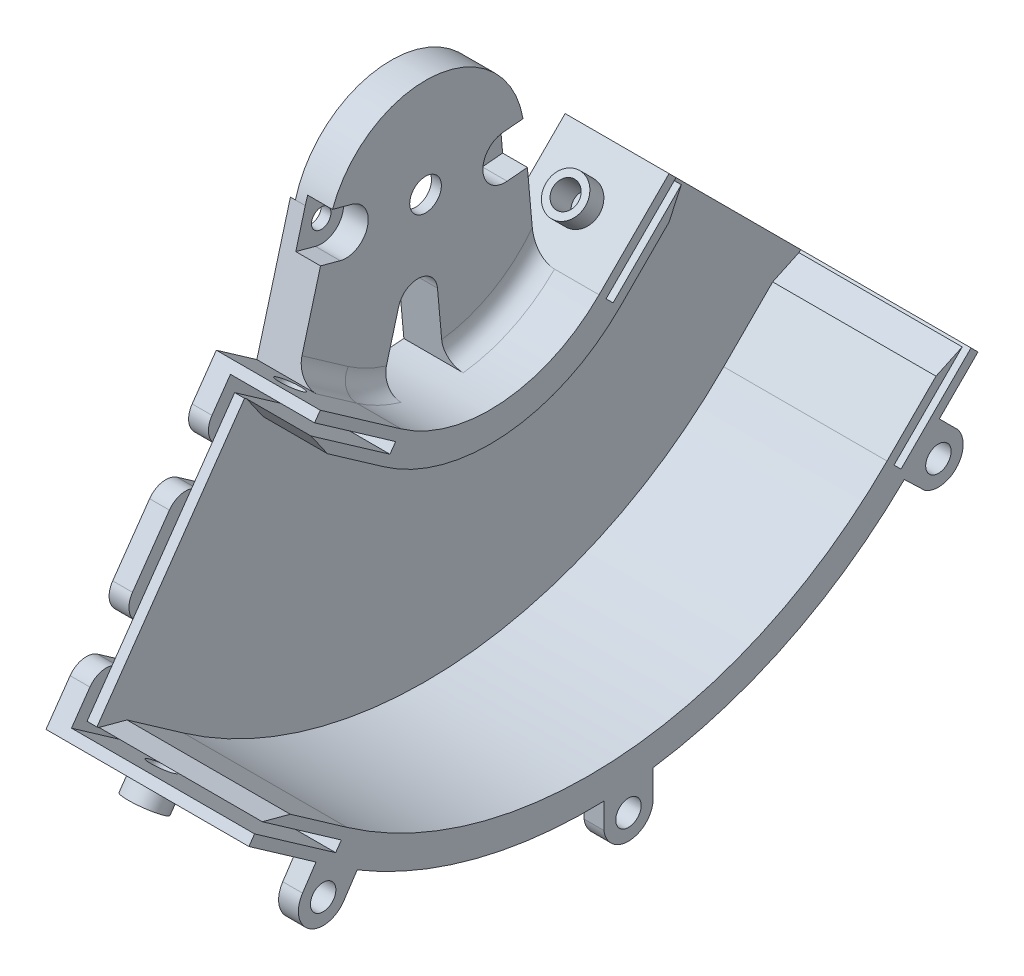
SolidWorks part; units mm, degrees
ref_plane "Front Plane" through (0, 0, 0) normal (0, 0, 1) x (1, 0, 0)
ref_plane "Top Plane" through (0, 0, 0) normal (0, 1, 0) x (1, 0, 0)
ref_plane "Right Plane" through (0, 0, 0) normal (1, 0, 0) x (0, 0, -1)
sketch "Sketch3" plane through (0, 0, 0) normal (1, 0, 0) x (0, 0, -1)
  line L0 (-22.7274, -32.4581) -> (-62.0633, -88.6355)
  line L1 (28.0184, -28.0184) -> (76.5118, -76.5118)
  line L2 (-22.7274, -32.4581) -> (0, 0) construction
  line L3 (0, 0) -> (28.0184, -28.0184) construction
  line L4 (0, 40.513) -> (0, -40.513) construction
  line L5 (-62.0633, -88.6355) -> (-66.4339, -94.8775)
  line L6 (76.5118, -76.5118) -> (81.8999, -81.8999)
  arc A2 (-62.0633, -88.6355) -> (76.5118, -76.5118) centre (0, 0) ccw
  arc A4 (-27.098, -38.7) -> (33.4066, -33.4066) centre (0, 0) ccw
  arc A5 (-22.7274, -32.4581) -> (28.0184, -28.0184) centre (0, 0) ccw
  arc A6 (-66.4339, -94.8775) -> (81.8999, -81.8999) centre (0, 0) ccw
  dimension "D1" = 216.408
  dimension "D2" = 135
  dimension "D3" = 94.488
  dimension "D4" = 7.62
  dimension "D6" = 7.62
  dimension "D5" = 80
extrude "Base extrude" add sketch "Sketch3" along normal blind 58.42 contours L5 A6 L6 A2 | A5 L0 A4 L1 region at (0, -39.9408, -3.4944) region at (0, -109.321, -9.5643)
sketch "Sketch4" plane through (58.42, 0, 0) normal (1, 0, 0) x (0, 0, -1)
  line L0 (-66.4339, -94.8775) -> (-22.7274, -32.4581)
  line L1 (28.0184, -28.0184) -> (81.8999, -81.8999)
  arc A0 (-22.7274, -32.4581) -> (28.0184, -28.0184) centre (0, 0) ccw
  arc A1 (-22.7274, -32.4581) -> (28.0184, -28.0184) centre (0, 0) ccw construction
  arc A2 (-66.4339, -94.8775) -> (81.8999, -81.8999) centre (0, 0) ccw
  arc A3 (-66.4339, -94.8775) -> (81.8999, -81.8999) centre (0, 0) ccw construction
  arc M1 (28.0184, -28.0184) -> (-22.7274, -32.4581) centre (0, 0) cw
  line M2 (-22.7274, -32.4581) -> (-27.098, -38.7)
  arc M3 (-27.098, -38.7) -> (33.4066, -33.4066) centre (0, 0) ccw
  line M4 (33.4066, -33.4066) -> (28.0184, -28.0184)
extrude "Outer wall" add sketch "Sketch4" along normal blind 7.62 contours L0 A2 L1 M3 | M4 M1 M2 M3 region at (58.42, -79.1939, -6.9286) region at (58.42, -39.9408, -3.4944)
ref_plane "Midplane" through (29.21, 0, 0) normal (-1, 0, 0) x (0, 0, 1)
mirror "Mirror1" about plane through (29.21, 0, 0) normal (-1, 0, 0) of "Outer wall"
sketch "Sketch6" plane through (0, 0, 0) normal (0, 0.5736, 0.8192) x (1, 0, 0)
  line L27 (-5.08, -42.164) -> (63.5, -42.164)
  line L28 (-5.08, -42.164) -> (-5.08, -113.284)
  line L29 (-5.08, -113.284) -> (63.5, -113.284)
  line L30 (63.5, -42.164) -> (63.5, -113.284)
  line L31 (-2.54, -44.704) -> (60.96, -44.704)
  line L32 (-2.54, -44.704) -> (-2.54, -110.744)
  line L33 (-2.54, -110.744) -> (60.96, -110.744)
  line L34 (60.96, -44.704) -> (60.96, -110.744)
  line L35 (58.42, -47.244) -> (0, -47.244) construction
  line L36 (0, -108.204) -> (0, -18.7894) construction
  line L37 (58.42, -18.7894) -> (58.42, -108.204) construction
  line L38 (58.42, -108.204) -> (0, -108.204) construction
  line L40 (0, -47.244) -> (58.42, -47.244)
  line L41 (0, -47.244) -> (0, -108.204)
  line L42 (0, -108.204) -> (58.42, -108.204)
  line L43 (58.42, -47.244) -> (58.42, -108.204)
  line L44 (-7.62, -39.624) -> (66.04, -39.624)
  line L45 (-7.62, -39.624) -> (-7.62, -115.824)
  line L46 (-7.62, -115.824) -> (66.04, -115.824)
  line L47 (66.04, -39.624) -> (66.04, -115.824)
  line M21 (-7.62, -39.624) -> (-7.62, -115.824)
  line M22 (-7.62, -115.824) -> (66.04, -115.824)
  line M23 (66.04, -115.824) -> (66.04, -39.624)
  line M24 (66.04, -39.624) -> (-7.62, -39.624)
  line M25 (58.42, -108.204) -> (0, -108.204)
  line M26 (0, -108.204) -> (0, -47.244)
  line M27 (0, -47.244) -> (58.42, -47.244)
  line M28 (58.42, -47.244) -> (58.42, -108.204)
  dimension "D1" = 2.54
  dimension "D2" = 2.54
  dimension "D3" = 2.54
  dimension "D4" = 2.54
  dimension "D5" = 2.54
  dimension "D6" = 2.54
  dimension "D7" = 2.54
  dimension "D8" = 2.54
extrude "Endcap 1" add sketch "Sketch6" along normal blind 25.4 contours L27 L30 L29 L28 M24 M21 M22 M23 | L34 L31 L32 L33 M28 M25 M26 M27 region at (29.21, -37.3698, 26.1667) region at (29.21, -33.3262, 23.3353)
sketch "Sketch7" plane through (0, 0, 0) normal (0, 0.7071, -0.7071) x (1, 0, 0)
  line L0 (-5.08, 113.284) -> (63.5, 113.284)
  line L1 (-5.08, 113.284) -> (-5.08, 42.164)
  line L2 (-5.08, 42.164) -> (63.5, 42.164)
  line L3 (63.5, 113.284) -> (63.5, 42.164)
  line L4 (-2.54, 110.744) -> (60.96, 110.744)
  line L5 (-2.54, 110.744) -> (-2.54, 44.704)
  line L6 (-2.54, 44.704) -> (60.96, 44.704)
  line L7 (60.96, 110.744) -> (60.96, 44.704)
  line L8 (0, 108.204) -> (58.42, 108.204)
  line L9 (0, 108.204) -> (0, 47.244)
  line L10 (0, 47.244) -> (58.42, 47.244)
  line L11 (58.42, 108.204) -> (58.42, 47.244)
  line L12 (-7.62, 115.824) -> (66.04, 115.824)
  line L13 (-7.62, 115.824) -> (-7.62, 39.624)
  line L14 (-7.62, 39.624) -> (66.04, 39.624)
  line L15 (66.04, 115.824) -> (66.04, 39.624)
  line L16 (58.42, 108.204) -> (0, 108.204) construction
  line L17 (58.42, 47.244) -> (58.42, 108.204) construction
  line L18 (66.04, 115.824) -> (-7.62, 115.824) construction
  line L19 (66.04, 39.624) -> (66.04, 115.824) construction
  line L20 (-7.62, 39.624) -> (-7.62, 115.824) construction
  line L21 (66.04, 39.624) -> (-7.62, 39.624) construction
  line M17 (66.04, 115.824) -> (-7.62, 115.824)
  line M18 (-7.62, 115.824) -> (-7.62, 39.624)
  line M19 (-7.62, 39.624) -> (66.04, 39.624)
  line M20 (66.04, 39.624) -> (66.04, 115.824)
  line M21 (0, 47.244) -> (0, 108.204)
  line M22 (0, 108.204) -> (58.42, 108.204)
  line M23 (58.42, 108.204) -> (58.42, 47.244)
  line M24 (58.42, 47.244) -> (0, 47.244)
  dimension "D1" = 2.54
  dimension "D2" = 2.54
  dimension "D3" = 2.54
  dimension "D4" = 2.54
  dimension "D5" = 2.54
  dimension "D6" = 2.54
  dimension "D7" = 2.54
  dimension "D8" = 2.54
extrude "Endcap 2" add sketch "Sketch7" along normal blind 25.4 contours L0 L3 L2 L1 M20 M17 M18 M19 | L7 L4 L5 L6 M24 M21 M22 M23 region at (29.21, -77.66, -77.66) region at (29.21, -81.1505, -81.1505)
chamfer "Internal Chamfer" distance 7.62 angle 20 4 edges at (29.21, -74.0667, 82.8697) (29.21, -24.1312, 47.9045) (29.21, -58.5513, -94.4723) (29.21, -15.446, -51.3671) first distance on face at (29.21, -81.3511, 72.4665) first distance on face at (29.21, -31.4156, 37.5013) first distance on face at (29.21, -67.5315, -85.492) first distance on face at (29.21, -24.4263, -42.3868)
ref_plane "Plane2" through (0, -13.9736, -1.2225) normal (0, -0.9962, -0.0872) x (-1, 0, 0)
sketch "Sketch10" plane through (0, -13.9736, -1.2225) normal (0, -0.9962, -0.0872) x (-1, 0, 0)
  line L0 (-66.04, 93.9078) -> (7.62, 93.9078) construction
  line L1 (-16.51, 95.5358) -> (-41.91, 95.5358)
  line L2 (-16.51, 95.5358) -> (-16.51, -82.1857)
  line L3 (-16.51, -82.1857) -> (-41.91, -82.1857)
  line L4 (-41.91, 95.5358) -> (-41.91, -82.1857)
  point P4 (-29.21, 93.9078)
  point P5 (-29.21, 95.5358)
  dimension "D1" = 25.4
extrude "Flywheel Hole" cut sketch "Sketch10" along normal up to next
sketch "Sketch11" plane through (-7.62, 0, 0) normal (-1, 0, 0) x (0, 0, 1)
  line L0 (-25.2982, 2.2719) -> (-28.0184, -28.0184)
  line L4 (-3.0636, -22.3183) -> (-4.5937, -39.3568)
  line L5 (6.8995, -21.445) -> (11.3704, -37.9575)
  line L6 (-20.4217, -1.79) -> (20.4217, 1.79) construction
  line L7 (24.5172, 6.6383) -> (33.1306, -25.1737)
  line L8 (43.5339, -17.8892) -> (22.7274, -32.4581) construction
  line L10 (1.5525, -17.7121) -> (-2.2178, 25.303) construction
  line L11 (22.7274, -32.4581) -> (43.5339, -17.8892)
  line L12 (22.7274, -32.4581) -> (33.1306, -25.1737)
  arc A1 (-28.0184, -28.0184) -> (22.7274, -32.4581) centre (0, 0) ccw construction
  circle A3 centre (0, 0) radius 4.064
  arc A4 (24.5172, 6.6383) -> (-25.2982, 2.2719) centre (0, 0) ccw
  circle A6 centre (-20.4217, -1.79) radius 2.5
  circle A7 centre (20.4217, 1.79) radius 2.5
  arc A8 (-3.0636, -22.3183) -> (6.8995, -21.445) centre (1.9961, -22.7727) cw
  arc A11 (11.3704, -37.9575) -> (22.7274, -32.4581) centre (0, 0) ccw
  arc A12 (-28.0184, -28.0184) -> (22.7274, -32.4581) centre (0, 0) ccw
  arc A13 (-28.0184, -28.0184) -> (-4.5937, -39.3568) centre (0, 0) ccw
  point P22 (0, 0)
  dimension "D3" = 8.128
  dimension "D2" = 25.4
  dimension "D1" = 5
  dimension "D5" = 5.08
  dimension "D4" = 41
  dimension "D7" = 43.18
  dimension "D6" = 0
extrude "Flywheel holder" add sketch "Sketch11" against normal blind 7.62
sketch "Sketch12" plane through (-7.62, 0, 0) normal (-1, 0, 0) x (0, 0, 1)
  circle A0 centre (0, 0) radius 14.605
  dimension "D1" = 29.21
extrude "Motor insert" cut sketch "Sketch12" against normal blind 6.35
sketch "Sketch13" plane through (66.04, 0, 0) normal (1, 0, 0) x (0, 0, -1)
  line L1 (-110.5367, 4.1813) -> (110.9716, 4.1813)
  line L2 (-110.5367, 4.1813) -> (-110.5367, -123.3274)
  line L3 (-110.5367, -123.3274) -> (110.9716, -123.3274)
  line L4 (110.9716, 4.1813) -> (110.9716, -123.3274)
extrude "Cut-Extrude1" cut sketch "Sketch13" against normal up to surface (24.13 mm away) up to face at (41.91, -26.9401, -2.3569)
sketch "Sketch14" plane through (41.91, 0, 0) normal (1, 0, 0) x (0, 0, -1)
  line L0 (-73.4762, -97.5482) -> (-70.0245, -92.3633)
  line L1 (-66.4339, -94.8775) -> (-87.2404, -80.3086) construction
  line L2 (-70.0245, -92.3633) -> (-59.4528, -99.401)
  line L3 (-59.4528, -99.401) -> (-62.9045, -104.586)
  line L4 (3.8593, -122.286) -> (3.8593, -115.7597)
  line L5 (3.8593, -115.7597) -> (16.51, -114.6413)
  line L6 (16.51, -114.6413) -> (16.51, -121.4959)
  line L7 (86.1731, -87.8533) -> (80.953, -82.836)
  line L8 (80.953, -82.836) -> (89.843, -73.7664)
  line L10 (89.843, -73.7664) -> (94.5478, -78.4712)
  line L11 (99.8604, -63.9394) -> (81.8999, -81.8999) construction
  circle A0 centre (-68.1904, -101.0671) radius 3.2639
  circle A1 centre (89.7004, -82.5731) radius 3.2639
  circle A2 centre (10.16, -121.4959) radius 3.2639
  arc A3 (-73.4762, -97.5482) -> (-62.9045, -104.586) centre (-68.1904, -101.0671) ccw
  arc A4 (3.8593, -122.286) -> (16.51, -121.4959) centre (10.16, -121.4959) ccw
  arc A5 (86.1731, -87.8533) -> (93.8023, -77.7257) centre (89.7004, -82.5731) ccw
  arc A6 (-66.4339, -94.8775) -> (81.8999, -81.8999) centre (0, 0) ccw construction
  line M9 (-87.2404, -80.3086) -> (-66.4339, -94.8775)
  arc M10 (-66.4339, -94.8775) -> (81.8999, -81.8999) centre (0, 0) ccw
  line M11 (81.8999, -81.8999) -> (99.8604, -63.9394)
  dimension "D7" = 6.5278
  dimension "D8" = 12.7
  dimension "D1" = 121.92
  dimension "D2" = 121.92
  dimension "D3" = 19.05
  dimension "D4" = 10.16
  dimension "D5" = 121.92
  dimension "D6" = 10.16
  dimension "D9" = 12.7
  dimension "D10" = 12.7
  dimension "D11" = 12.7
extrude "Joining connectors" add sketch "Sketch14" against normal blind 5.08 contours L7 A5 L10 A1 M11 M10 | L0 A3 L3 A0 M10 M9 | L5 L6 A4 L4 | A2 region at (41.91, -82.521, -81.5777) region at (41.91, -95.0739, 71.573)
sketch "Sketch15" plane through (-7.62, 0, 0) normal (-1, 0, 0) x (0, 0, 1)
  line L0 (-35.56, -110.2301) -> (-35.56, -132.08)
  line L1 (-35.56, -132.08) -> (30.48, -132.08)
  line L2 (30.48, -132.08) -> (30.48, -111.7415)
  circle A0 centre (20.32, -121.92) radius 3.2639
  circle A1 centre (-25.4, -121.92) radius 3.2639
  arc A2 (-81.8999, -81.8999) -> (66.4339, -94.8775) centre (0, 0) ccw construction
  circle A4 centre (-10.16, -121.4959) radius 3.2639
  arc A5 (-81.8999, -81.8999) -> (66.4339, -94.8775) centre (0, 0) ccw
  arc A6 (-81.8999, -81.8999) -> (66.4339, -94.8775) centre (0, 0) ccw
  circle A7 centre (-10.16, -121.4959) radius 3.2639 construction
  arc M16 (-81.8999, -81.8999) -> (66.4339, -94.8775) centre (0, 0) ccw
  dimension "D1" = 6.5278
  dimension "D2" = 25.4
  dimension "D3" = 20.32
  dimension "D5" = 10.16
  dimension "D6" = 10.16
  dimension "D7" = 10.16
  dimension "D8" = 121.92
  dimension "D4" = 0
extrude "80-20 connectors" add sketch "Sketch15" against normal blind 5.08 contours L1 L2 L0 A4 A1 A0 M16 region at (-7.62, -123.2019, -2.8038)
fillet "Fillet1" radius 30.48 2 edges at (-5.08, -111.7415, 30.48) (-5.08, -110.2301, -35.56)
fillet "Fillet2" radius 15.24 2 edges at (-5.08, -132.08, -35.56) (-5.08, -132.08, 30.48)
sketch "Sketch18" plane through (-1.27, 0, 0) normal (-1, 0, 0) x (0, 0, 1)
  circle A0 centre (0, 0) radius 4.064
  circle A1 centre (0, 0) radius 14.605
  circle A2 centre (0, 0) radius 14.605 construction
  circle A3 centre (0, 0) radius 4.064 construction
extrude "Boss-Extrude3" add sketch "Sketch18" along normal blind 1.27
sketch "Sketch20" plane through (-7.62, 0, 0) normal (-1, 0, 0) x (0, 0, 1)
  line L5 (6.8995, -21.445) -> (11.3704, -37.9575)
  line L6 (-4.5937, -39.3568) -> (-3.0636, -22.3183)
  line L7 (6.8995, -21.445) -> (7.6509, -24.2203)
  line L8 (-3.3207, -25.182) -> (-3.0636, -22.3183)
  circle A0 centre (0, 0) radius 14.605
  arc A1 (7.6509, -24.2203) -> (-3.3207, -25.182) centre (0, 0) ccw
  circle A2 centre (20.4217, 1.79) radius 2.5
  circle A3 centre (-20.4217, -1.79) radius 2.5
  circle A4 centre (-20.4217, -1.79) radius 2.5 construction
  circle A5 centre (20.4217, 1.79) radius 2.5 construction
  arc A6 (24.5172, 6.6383) -> (-25.2982, 2.2719) centre (0, 0) ccw construction
  circle A7 centre (0, 0) radius 14.605 construction
  arc A12 (6.8995, -21.445) -> (-3.0636, -22.3183) centre (1.9961, -22.7727) ccw
  arc A13 (6.8995, -21.445) -> (-3.0636, -22.3183) centre (1.9961, -22.7727) ccw
  dimension "D1" = 0
extrude "Boss-Extrude5" add sketch "Sketch20" along normal blind 1.27
sketch "Sketch21" plane through (0, 0, 0) normal (1, 0, 0) x (0, 0, -1)
  line L12 (-20.4217, 1.79) -> (20.4217, -1.79) construction
  line L13 (-21.9153, -3.7264) -> (-30.8883, -1.2968)
  line L14 (-33.1306, -25.1737) -> (-24.5172, 6.6383) construction
  line L15 (-30.8883, -1.2968) -> (-27.8167, 9.713)
  line L16 (-27.8167, 9.713) -> (-18.9281, 7.3064)
  line L17 (20.9329, -7.4821) -> (30.9171, -6.5855)
  line L18 (25.2982, 2.2719) -> (28.0184, -28.0184) construction
  line L19 (30.9171, -6.5855) -> (29.8077, 4.7909)
  line L20 (29.8077, 4.7909) -> (19.9105, 3.9021)
  arc A2 (-21.9153, -3.7264) -> (-18.9281, 7.3064) centre (-20.4217, 1.79) ccw
  arc A3 (19.9105, 3.9021) -> (20.9329, -7.4821) centre (20.4217, -1.79) ccw
  dimension "D1" = 11.43
extrude "Cut-Extrude2" cut sketch "Sketch21" against normal blind 6.35
sketch "Sketch22" plane through (-7.62, 0, 0) normal (-1, 0, 0) x (0, 0, 1)
  line L0 (-63.4904, -27.5694) -> (-57.2042, -21.2832)
  line L1 (-99.8604, -63.9394) -> (-45.9789, -10.0579) construction
  line L2 (-57.2042, -21.2832) -> (-42.3868, -36.1006)
  line L3 (-63.4904, -27.5694) -> (-48.673, -42.3868)
  line L4 (-73.8177, -67.5315) -> (-88.6351, -52.7141)
  line L5 (-88.6351, -52.7141) -> (-82.3489, -46.4279)
  line L6 (-82.3489, -46.4279) -> (-67.5315, -61.2453)
  line L7 (52.6394, -30.8933) -> (35.474, -42.9126)
  line L8 (43.5339, -17.8892) -> (87.2404, -80.3086) construction
  line L9 (52.6394, -30.8933) -> (57.7385, -38.1755)
  line L10 (57.7385, -38.1755) -> (40.5731, -50.1948)
  line L11 (55.8704, -72.0416) -> (73.0358, -60.0223)
  line L12 (73.0358, -60.0223) -> (78.1349, -67.3046)
  line L13 (78.1349, -67.3046) -> (60.9695, -79.3239)
  line L14 (-45.9789, -10.0579) -> (-28.0184, -28.0184) construction
  line L15 (-99.8604, -63.9394) -> (-81.8999, -81.8999) construction
  line L16 (43.5339, -17.8892) -> (33.1306, -25.1737) construction
  line L17 (87.2404, -80.3086) -> (66.4339, -94.8775) construction
  line L18 (-80.1039, -80.1039) -> (-29.8145, -29.8145) construction
  arc A0 (-73.8177, -67.5315) -> (-67.5315, -61.2453) centre (-70.6746, -64.3884) ccw
  arc A1 (-48.673, -42.3868) -> (-42.3868, -36.1006) centre (-45.5299, -39.2437) ccw
  arc A2 (35.474, -42.9126) -> (40.5731, -50.1948) centre (38.0236, -46.5537) ccw
  arc A3 (55.8704, -72.0416) -> (60.9695, -79.3239) centre (58.42, -75.6827) ccw
  dimension "D1" = 8.89
  dimension "D3" = 20.32
  dimension "D4" = 20.32
  dimension "D5" = 20.32
  dimension "D6" = 20.32
extrude "support removal" cut sketch "Sketch22" against normal up to next
fillet "Fillet4" radius 5.08 8 edges at (-6.35, -60.0223, 73.0358) (-6.35, -67.3046, 78.1349) (-6.35, -38.1755, 57.7385) (-6.35, -30.8933, 52.6394) (-6.35, -46.4279, -82.3489) (-6.35, -52.7141, -88.6351) (-6.35, -27.5694, -63.4904) (-6.35, -21.2832, -57.2042)
sketch "Sketch23" plane through (-7.62, 0, 0) normal (-1, 0, 0) x (0, 0, 1)
  line L0 (-78.7568, -42.8358) -> (-67.0825, -31.1615) construction
  line L1 (60.6522, -42.3368) -> (70.122, -55.861) construction
  line L2 (-72.9197, -36.9987) -> (-63.9394, -45.9789) construction
  line L3 (54.9839, -56.3834) -> (65.3871, -49.0989) construction
  line L4 (46.4476, -22.0505) -> (84.3266, -76.1473) construction
  line L5 (-67.5315, -67.5315) -> (-42.3868, -42.3868) construction
  line L6 (34.3825, -49.1033) -> (54.7788, -78.2323) construction
  circle A0 centre (-63.9394, -45.9789) radius 3.2639
  circle A1 centre (54.9839, -56.3834) radius 3.2639
  point P0 (-72.9197, -36.9987)
  point P1 (65.3871, -49.0989)
  dimension "D1" = 6.5278
  dimension "D2" = 12.7
  dimension "D3" = 12.7
extrude "Cut-Extrude3" cut sketch "Sketch23" against normal up to next contours A1 | A0 region at (-7.62, -45.9789, -63.9394) region at (-7.62, -56.3834, 54.9839)
sketch "Sketch24" plane through (0, -81.8999, -81.8999) normal (0, -0.7071, -0.7071) x (1, 0, 0)
  line L0 (36.83, 0) -> (-7.62, 0) construction
  line L1 (-5.08, -25.4) -> (-5.08, 0) construction
  circle A0 centre (7.62, -12.7) radius 3.2639
  dimension "D3" = 6.5278
  dimension "D1" = 12.7
  dimension "D2" = 12.7
extrude "Cut-Extrude4" cut sketch "Sketch24" against normal up to next contours A0
ref_plane "Plane3" through (0, -54.9592, -54.9592) normal (0, 0.7071, 0.7071) x (1, 0, 0)
sketch "Sketch26" plane through (0, -94.8775, 66.4339) normal (0, -0.8192, 0.5736) x (1, 0, 0)
  line L0 (-5.08, 25.4) -> (-5.08, 0) construction
  line L1 (36.83, 0) -> (-7.62, 0) construction
  circle A0 centre (7.62, 12.7) radius 3.2639
  dimension "D1" = 6.5278
  dimension "D2" = 12.7
  dimension "D3" = 12.7
extrude "Cut-Extrude5" cut sketch "Sketch26" against normal up to next
ref_plane "Plane4" through (0, -63.6678, 44.5807) normal (0, -0.8192, 0.5736) x (-1, 0, 0)
sketch "Sketch27" plane through (0, -28.0184, -28.0184) normal (0, 0.7071, 0.7071) x (1, 0, 0)
  line L0 (16.51, 0) -> (0, 0) construction
  line L1 (-5.08, 25.4) -> (-5.08, 0) construction
  circle A0 centre (2.54, 12.7) radius 3.2639
  dimension "D1" = 6.5278
  dimension "D2" = 12.7
  dimension "D3" = 7.62
extrude "Cut-Extrude6" cut sketch "Sketch27" against normal up to next
sketch "Sketch28" plane through (0, -32.4581, 22.7274) normal (0, 0.8192, -0.5736) x (1, 0, 0)
  line L0 (16.51, 0) -> (0, 0) construction
  line L1 (-5.08, -25.4) -> (-5.08, 0) construction
  circle A0 centre (2.54, -17.78) radius 3.2639
  dimension "D2" = 6.5278
  dimension "D1" = 17.78
  dimension "D3" = 7.62
extrude "Cut-Extrude7" cut sketch "Sketch28" against normal up to next contours A0
sketch "Sketch29" plane through (-7.62, 0, 0) normal (-1, 0, 0) x (0, 0, 1)
  line L46 (55.8704, -72.0416) -> (68.8745, -62.9361)
  line L47 (70.122, -55.861) -> (60.6522, -42.3368)
  line L48 (53.5772, -41.0893) -> (40.5731, -50.1948)
  line L49 (35.474, -42.9126) -> (48.4781, -33.807)
  line L50 (49.7256, -26.732) -> (43.5339, -17.8892)
  line L51 (43.5339, -17.8892) -> (33.1306, -25.1737)
  line L52 (33.1306, -25.1737) -> (24.5172, 6.6383)
  line L53 (7.6509, -24.2203) -> (11.3704, -37.9575)
  line L54 (-4.5937, -39.3568) -> (-3.3207, -25.182)
  line L55 (-25.2982, 2.2719) -> (-28.0184, -28.0184)
  line L56 (-28.0184, -28.0184) -> (-45.9789, -10.0579)
  line L57 (-45.9789, -10.0579) -> (-53.6121, -17.6911)
  line L58 (-53.6121, -24.8753) -> (-42.3868, -36.1006)
  line L59 (-48.673, -42.3868) -> (-59.8983, -31.1615)
  line L60 (-67.0825, -31.1615) -> (-78.7568, -42.8358)
  line L61 (-78.7568, -50.02) -> (-67.5315, -61.2453)
  line L62 (-73.8177, -67.5315) -> (-85.043, -56.3062)
  line L63 (-92.2272, -56.3062) -> (-99.8604, -63.9394)
  line L64 (-99.8604, -63.9394) -> (-81.8999, -81.8999)
  line L65 (-22.4243, -132.08) -> (18.1792, -132.08)
  line L66 (66.4339, -94.8775) -> (87.2404, -80.3086)
  line L67 (87.2404, -80.3086) -> (81.0486, -71.4659)
  line L68 (73.9736, -70.2184) -> (60.9695, -79.3239)
  line L69 (55.8704, -72.0416) -> (68.8745, -62.9361)
  line L70 (70.122, -55.861) -> (60.6522, -42.3368)
  line L71 (53.5772, -41.0893) -> (40.5731, -50.1948)
  line L72 (35.474, -42.9126) -> (48.4781, -33.807)
  line L73 (49.7256, -26.732) -> (43.5339, -17.8892)
  line L74 (43.5339, -17.8892) -> (33.1306, -25.1737)
  line L75 (33.1306, -25.1737) -> (24.5172, 6.6383)
  line L76 (7.6509, -24.2203) -> (11.3704, -37.9575)
  line L77 (-4.5937, -39.3568) -> (-3.3207, -25.182)
  line L78 (-25.2982, 2.2719) -> (-28.0184, -28.0184)
  line L79 (-28.0184, -28.0184) -> (-45.9789, -10.0579)
  line L80 (-45.9789, -10.0579) -> (-53.6121, -17.6911)
  line L81 (-53.6121, -24.8753) -> (-42.3868, -36.1006)
  line L82 (-48.673, -42.3868) -> (-59.8983, -31.1615)
  line L83 (-67.0825, -31.1615) -> (-78.7568, -42.8358)
  line L84 (-78.7568, -50.02) -> (-67.5315, -61.2453)
  line L85 (-73.8177, -67.5315) -> (-85.043, -56.3062)
  line L86 (-92.2272, -56.3062) -> (-99.8604, -63.9394)
  line L87 (-99.8604, -63.9394) -> (-81.8999, -81.8999)
  line L88 (-22.4243, -132.08) -> (18.1792, -132.08)
  line L89 (66.4339, -94.8775) -> (87.2404, -80.3086)
  line L90 (87.2404, -80.3086) -> (81.0486, -71.4659)
  line L91 (73.9736, -70.2184) -> (60.9695, -79.3239)
  arc A21 (7.6509, -24.2203) -> (24.5172, 6.6383) centre (0, 0) ccw
  arc A22 (7.6509, -24.2203) -> (24.5172, 6.6383) centre (0, 0) ccw
  arc A23 (-25.2982, 2.2719) -> (-3.3207, -25.182) centre (0, 0) ccw
  arc A24 (-25.2982, 2.2719) -> (-3.3207, -25.182) centre (0, 0) ccw
  arc A42 (68.8745, -62.9361) -> (70.122, -55.861) centre (65.9607, -58.7748) ccw
  arc A43 (60.6522, -42.3368) -> (53.5772, -41.0893) centre (56.491, -45.2506) ccw
  arc A44 (35.474, -42.9126) -> (40.5731, -50.1948) centre (38.0236, -46.5537) ccw
  arc A45 (48.4781, -33.807) -> (49.7256, -26.732) centre (45.5643, -29.6458) ccw
  arc A47 (-4.5937, -39.3568) -> (11.3704, -37.9575) centre (0, 0) ccw
  arc A49 (-53.6121, -17.6911) -> (-53.6121, -24.8753) centre (-50.02, -21.2832) ccw
  arc A50 (-48.673, -42.3868) -> (-42.3868, -36.1006) centre (-45.5299, -39.2437) ccw
  arc A51 (-59.8983, -31.1615) -> (-67.0825, -31.1615) centre (-63.4904, -34.7536) ccw
  arc A52 (-78.7568, -42.8358) -> (-78.7568, -50.02) centre (-75.1647, -46.4279) ccw
  arc A53 (-73.8177, -67.5315) -> (-67.5315, -61.2453) centre (-70.6746, -64.3884) ccw
  arc A54 (-85.043, -56.3062) -> (-92.2272, -56.3062) centre (-88.6351, -59.8983) ccw
  arc A55 (-81.8999, -81.8999) -> (-52.2817, -103.3529) centre (0, 0) ccw
  arc A56 (-36.9629, -121.4104) -> (-52.2817, -103.3529) centre (-66.04, -130.5511) ccw
  arc A57 (-36.9629, -121.4104) -> (-22.4243, -132.08) centre (-22.4243, -116.84) ccw
  arc A58 (18.1792, -132.08) -> (32.4348, -122.2285) centre (18.1792, -116.84) ccw
  arc A59 (48.2489, -105.296) -> (32.4348, -122.2285) centre (60.9459, -133.0055) ccw
  arc A60 (48.2489, -105.296) -> (66.4339, -94.8775) centre (0, 0) ccw
  arc A61 (81.0486, -71.4659) -> (73.9736, -70.2184) centre (76.8873, -74.3796) ccw
  arc A62 (55.8704, -72.0416) -> (60.9695, -79.3239) centre (58.42, -75.6827) ccw
  arc A63 (68.8745, -62.9361) -> (70.122, -55.861) centre (65.9607, -58.7748) ccw
  arc A64 (60.6522, -42.3368) -> (53.5772, -41.0893) centre (56.491, -45.2506) ccw
  arc A65 (35.474, -42.9126) -> (40.5731, -50.1948) centre (38.0236, -46.5537) ccw
  arc A66 (48.4781, -33.807) -> (49.7256, -26.732) centre (45.5643, -29.6458) ccw
  arc A68 (-4.5937, -39.3568) -> (11.3704, -37.9575) centre (0, 0) ccw
  arc A70 (-53.6121, -17.6911) -> (-53.6121, -24.8753) centre (-50.02, -21.2832) ccw
  arc A71 (-48.673, -42.3868) -> (-42.3868, -36.1006) centre (-45.5299, -39.2437) ccw
  arc A72 (-59.8983, -31.1615) -> (-67.0825, -31.1615) centre (-63.4904, -34.7536) ccw
  arc A73 (-78.7568, -42.8358) -> (-78.7568, -50.02) centre (-75.1647, -46.4279) ccw
  arc A74 (-73.8177, -67.5315) -> (-67.5315, -61.2453) centre (-70.6746, -64.3884) ccw
  arc A75 (-85.043, -56.3062) -> (-92.2272, -56.3062) centre (-88.6351, -59.8983) ccw
  arc A76 (-81.8999, -81.8999) -> (-52.2817, -103.3529) centre (0, 0) ccw
  arc A77 (-36.9629, -121.4104) -> (-52.2817, -103.3529) centre (-66.04, -130.5511) ccw
  arc A78 (-36.9629, -121.4104) -> (-22.4243, -132.08) centre (-22.4243, -116.84) ccw
  arc A79 (18.1792, -132.08) -> (32.4348, -122.2285) centre (18.1792, -116.84) ccw
  arc A80 (48.2489, -105.296) -> (32.4348, -122.2285) centre (60.9459, -133.0055) ccw
  arc A81 (48.2489, -105.296) -> (66.4339, -94.8775) centre (0, 0) ccw
  arc A82 (81.0486, -71.4659) -> (73.9736, -70.2184) centre (76.8873, -74.3796) ccw
  arc A83 (55.8704, -72.0416) -> (60.9695, -79.3239) centre (58.42, -75.6827) ccw
  circle A94 centre (-63.9394, -45.9789) radius 3.2639
  circle A95 centre (-63.9394, -45.9789) radius 3.2639
  circle A97 centre (54.9839, -56.3834) radius 3.2639
  circle A98 centre (54.9839, -56.3834) radius 3.2639
  circle A100 centre (-25.4, -121.92) radius 3.2639
  circle A101 centre (-25.4, -121.92) radius 3.2639
  circle A103 centre (-10.16, -121.4959) radius 3.2639
  circle A104 centre (-10.16, -121.4959) radius 3.2639
  circle A106 centre (20.32, -121.92) radius 3.2639
  circle A107 centre (20.32, -121.92) radius 3.2639
  dimension "D1" = 0
  dimension "D2" = 0
  dimension "D3" = 0
  dimension "D4" = 0
  dimension "D5" = 0
  dimension "D6" = 0
extrude "Boss-Extrude6" add sketch "Sketch29" along normal blind 2.54
sketch "Sketch31" plane through (0, -28.0184, -28.0184) normal (0, 0.7071, 0.7071) x (1, 0, 0)
  circle A0 centre (2.54, 12.7) radius 3.2639
  circle A1 centre (2.54, 12.7) radius 5.08
  circle A2 centre (2.54, 12.7) radius 3.2639 construction
  dimension "D1" = 10.16
extrude "Boss-Extrude8" add sketch "Sketch31" along normal blind 5.08
sketch "Sketch32" plane through (0, -81.8999, -81.8999) normal (0, -0.7071, -0.7071) x (1, 0, 0)
  circle A0 centre (7.62, -12.7) radius 3.2639
  circle A1 centre (7.62, -12.7) radius 5.08
  circle A2 centre (7.62, -12.7) radius 3.2639 construction
  dimension "D1" = 10.16
extrude "Boss-Extrude9" add sketch "Sketch32" along normal blind 5.08
sketch "Sketch33" plane through (0, -94.8775, 66.4339) normal (0, -0.8192, 0.5736) x (1, 0, 0)
  circle A0 centre (7.62, 12.7) radius 3.2639
  circle A1 centre (7.62, 12.7) radius 5.08
  circle A2 centre (7.62, 12.7) radius 3.2639 construction
  dimension "D1" = 10.16
extrude "Boss-Extrude10" add sketch "Sketch33" along normal blind 5.08
fillet "Fillet5" radius 5.08 3 edges at (0, -28.8159, 27.929) (0, -35.6628, 17.2692) (0, -35.6656, -17.2635)
